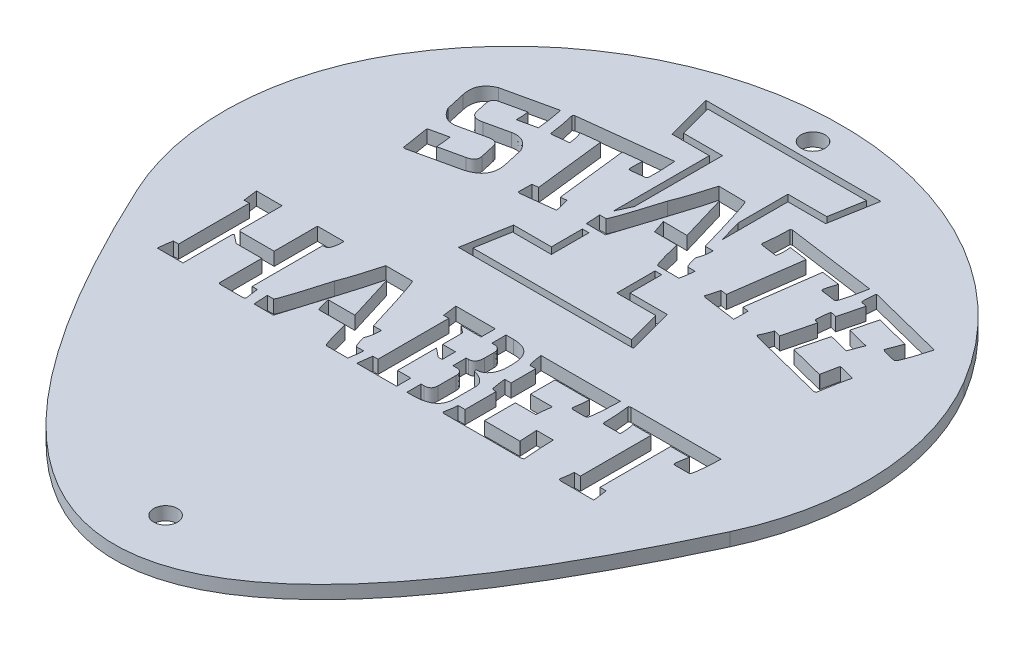
SolidWorks part; units mm, degrees
ref_plane "Front Plane" through (0, 0, 0) normal (0, 0, 1) x (1, 0, 0)
ref_plane "Top Plane" through (0, 0, 0) normal (0, 1, 0) x (1, 0, 0)
ref_plane "Right Plane" through (0, 0, 0) normal (1, 0, 0) x (0, 0, -1)
sketch "Sketch1" plane through (0, 0, 0) normal (0, 1, 0) x (1, 0, 0)
  arc A1 (105.41, 0) -> (-21.59, 0) centre (41.91, 0) ccw
  spline S0 degree 2 poles (-21.59, 0) (41.91, -152.4) (105.41, 0) knots 0 0 0 1 1 1
  dimension "D1" = 63.5
extrude "Boss-Extrude1" add sketch "Sketch1" along normal blind 2.54 contours S0 A1
fillet "Fillet1" radius 50.8 2 edges at (-21.59, 1.27, 0) (105.41, 1.27, 0)
sketch "Sketch2" plane through (0, 2.54, 0) normal (0, 1, 0) x (1, 0, 0)
  line L0 (-19.7843, 6.5271) -> (103.6043, 6.5271) construction
  line L1 (-3.3717, -3.6766) -> (1.5633, -3.6766)
  line L2 (1.5633, -3.6766) -> (1.5633, -11.6703)
  line L3 (1.8983, -12.0053) -> (8.3626, -12.0053)
  line L4 (8.3626, -12.0053) -> (8.3626, -3.6766)
  line L5 (8.3626, -3.6766) -> (13.471, -3.6766)
  line L6 (12.4462, -6.4043) -> (12.1151, -6.4043)
  line L7 (12.1151, -6.4043) -> (12.1151, -19.999)
  line L8 (12.1151, -19.999) -> (13.1241, -19.999)
  line L9 (13.471, -22.5532) -> (13.1241, -22.7266)
  line L10 (13.1241, -22.7266) -> (8.7095, -22.7266)
  line L11 (8.3626, -22.3798) -> (8.3626, -14.3861)
  line L12 (8.3626, -14.3861) -> (3.4277, -14.3861)
  line L13 (3.4277, -14.3861) -> (1.7367, -13.0302)
  line L14 (1.7367, -13.0302) -> (1.5633, -13.3731)
  line L15 (1.5633, -13.3731) -> (1.5633, -22.7266)
  line L16 (1.5633, -22.7266) -> (-3.3717, -22.7266)
  line L17 (-3.0248, -19.999) -> (-2.0158, -19.999)
  line L18 (-2.0158, -19.999) -> (-2.0158, -6.4043)
  line L19 (-2.0158, -6.4043) -> (-3.0248, -6.4043)
  line L20 (21.508, -3.6885) -> (26.6046, -3.6885)
  line L21 (30.3413, -14.9025) -> (31.8706, -14.9025)
  line L22 (31.8706, -14.9025) -> (31.8706, -15.0759)
  line L23 (32.2175, -20.0108) -> (33.5734, -20.0108)
  line L24 (33.2305, -22.7266) -> (29.1588, -22.7266)
  line L25 (27.456, -17.4566) -> (22.3594, -17.4566)
  line L26 (21.6696, -14.9025) -> (26.778, -14.9025)
  line L27 (26.778, -14.9025) -> (24.0504, -6.0692)
  line L28 (24.0504, -6.0692) -> (23.8888, -6.0692)
  line L29 (18.9538, -22.7266) -> (15.2171, -22.7266)
  line L30 (15.2171, -22.7266) -> (15.2171, -22.5532)
  line L31 (15.0437, -20.0108) -> (16.2262, -20.0108)
  line L32 (34.9727, -3.6766) -> (42.5426, -3.6766)
  line L33 (50.1126, -7.9336) -> (50.1126, -9.463)
  line L34 (47.5584, -12.3483) -> (47.5584, -12.6951)
  line L35 (50.286, -15.2375) -> (50.286, -19.321)
  line L36 (45.694, -22.7266) -> (44.6065, -22.7266)
  line L37 (35.3196, -19.999) -> (36.3286, -19.999)
  line L38 (36.3286, -19.999) -> (36.3286, -6.4043)
  line L39 (36.3286, -6.4043) -> (35.3196, -6.4043)
  line L40 (40.0811, -7.5868) -> (40.0811, -11.3274)
  line L41 (40.0811, -11.3274) -> (42.5426, -11.3274)
  line L42 (46.3719, -9.6246) -> (46.3719, -7.7602)
  line L43 (45.5206, -6.4043) -> (44.6065, -6.4043)
  line L44 (40.0811, -12.5217) -> (40.0811, -19.999)
  line L45 (40.0811, -19.999) -> (42.6294, -19.999)
  line L46 (46.5336, -18.6431) -> (46.5336, -15.2375)
  line L47 (45.1776, -13.8816) -> (44.6065, -13.8816)
  line L48 (41.772, -13.8816) -> (40.0811, -12.5217)
  line L49 (51.37, -3.716) -> (66.6439, -3.716)
  line L50 (65.962, -9.664) -> (63.4235, -9.664)
  line L51 (63.4235, -9.664) -> (63.0767, -9.4906)
  line L52 (63.4235, -6.4318) -> (56.7976, -6.4318)
  line L53 (56.7976, -6.4318) -> (56.7976, -11.1776)
  line L54 (56.7976, -11.1776) -> (61.0428, -11.1776)
  line L55 (60.7077, -14.0668) -> (56.7976, -14.0668)
  line L56 (56.7976, -14.0668) -> (56.7976, -20.0108)
  line L57 (56.7976, -20.0108) -> (63.597, -20.0108)
  line L58 (63.597, -20.0108) -> (63.597, -19.8413)
  line L59 (63.4235, -16.621) -> (66.6439, -16.621)
  line L60 (66.9868, -22.5532) -> (66.6439, -22.7266)
  line L61 (66.6439, -22.7266) -> (51.7168, -22.7266)
  line L62 (51.7168, -22.7266) -> (51.37, -22.5532)
  line L63 (51.7168, -20.0108) -> (53.0728, -20.0108)
  line L64 (53.0728, -20.0108) -> (53.0728, -14.0668)
  line L65 (51.8745, -11.1776) -> (53.0728, -11.1776)
  line L66 (53.0728, -11.1776) -> (53.0728, -6.4318)
  line L67 (53.0728, -6.4318) -> (52.0479, -6.4318)
  line L68 (68.6186, -3.6766) -> (85.9658, -3.6766)
  line L69 (85.2879, -9.1161) -> (82.5602, -9.1161)
  line L70 (82.5602, -6.4043) -> (78.9931, -6.4043)
  line L71 (78.9931, -6.4043) -> (78.9931, -19.999)
  line L72 (78.9931, -19.999) -> (80.1795, -19.999)
  line L73 (80.5224, -22.7266) -> (74.0581, -22.7266)
  line L74 (74.0581, -22.7266) -> (73.7112, -22.5532)
  line L75 (74.0581, -19.999) -> (75.2445, -19.999)
  line L76 (75.2445, -19.999) -> (75.2445, -6.4043)
  line L77 (75.2445, -6.4043) -> (71.6773, -6.4043)
  line L78 (72.0084, -9.1161) -> (68.9497, -9.1161)
  line L79 (68.2718, -3.8501) -> (68.6186, -3.6766)
  line L80 (42.5426, -6.4043) -> (38.7094, -6.4043)
  line L82 (42.6294, -19.999) -> (42.6294, -22.7266)
  line L84 (44.6065, -19.999) -> (44.6065, -22.7266)
  line L86 (44.6065, -13.8816) -> (44.6065, -11.3274)
  line L88 (42.5426, -13.8816) -> (42.5426, -11.3274)
  line L90 (44.6065, -6.4043) -> (44.6065, -3.6766)
  line L92 (42.5426, -6.4043) -> (42.5426, -3.6766)
  line L93 (44.6065, -11.3274) -> (45.0042, -11.3274)
  line L94 (42.5426, -13.8816) -> (41.772, -13.8816)
  line L95 (44.6065, -19.999) -> (45.1776, -19.999)
  line L96 (42.6294, -22.7266) -> (34.9727, -22.7266)
  line L97 (44.6065, -3.6766) -> (46.029, -3.6766)
  arc A0 (-12.5617, 32.6356) -> (-15.0576, -14.8714) centre (31.0157, 6.5271) ccw construction
  arc A1 (98.8776, -14.8714) -> (96.3817, 32.6356) centre (52.8043, 6.5271) ccw construction
  spline S0 degree 3 poles (1.5633, -11.6703) (1.5832, -11.7551) (1.6314, -11.9464) (1.818, -12.0103) (1.8983, -12.0053) knots 0 0 0 0 0.531818 1 1 1 1
  spline S1 degree 3 poles (13.471, -3.6766) (13.4667, -4.0745) (13.4563, -4.6352) (13.3372, -5.3157) (13.2327, -5.7059) (13.0884, -6.0101) (12.8646, -6.3061) (12.6103, -6.4071) (12.4462, -6.4043) knots 0 0 0 0 0.377825 0.528227 0.653888 0.759096 0.845794 1 1 1 1
  spline S2 degree 3 poles (13.1241, -19.999) (13.1205, -20.1062) (13.1483, -20.2919) (13.17, -20.5766) (13.215, -20.8686) (13.2577, -21.2152) (13.3552, -21.7812) (13.4101, -22.2356) (13.471, -22.5532) knots 0 0 0 0 0.124228 0.21791 0.332039 0.467782 0.624075 1 1 1 1
  spline S3 degree 3 poles (8.7095, -22.7266) (8.6245, -22.7242) (8.4039, -22.6854) (8.3651, -22.4648) (8.3626, -22.3798) knots 0 0 0 0 0.5 1 1 1 1
  spline S4 degree 3 poles (-3.3717, -22.7266) (-3.377, -22.5722) (-3.3506, -22.3245) (-3.3265, -21.9678) (-3.2826, -21.6466) (-3.2388, -21.2857) (-3.1444, -20.7336) (-3.0861, -20.298) (-3.0248, -19.999) knots 0 0 0 0 0.167857 0.271329 0.389634 0.521087 0.667537 1 1 1 1
  spline S5 degree 3 poles (-3.0248, -6.4043) (-3.085, -6.0443) (-3.1395, -5.5336) (-3.2374, -4.9018) (-3.2802, -4.5265) (-3.3252, -4.2199) (-3.3459, -3.9431) (-3.3736, -3.7707) (-3.3717, -3.6766) knots 0 0 0 0 0.397879 0.560026 0.697261 0.809965 0.897811 1 1 1 1
  spline S6 degree 3 poles (26.6046, -3.6885) (26.6726, -3.7251) (26.7428, -3.8697) (26.8553, -4.108) (26.9794, -4.4176) (27.1277, -4.8125) (27.3075, -5.293) (27.5004, -5.8639) (27.7237, -6.52) (27.9652, -7.265) (28.2404, -8.0962) (28.5287, -9.0174) (28.8448, -10.0253) (29.1891, -11.1185) (29.6866, -12.7557) (30.0827, -14.0236) (30.3413, -14.9025) knots 0 0 0 0 0.018773 0.039327 0.067393 0.103006 0.146294 0.197354 0.255675 0.321893 0.395795 0.477496 0.566465 0.663438 0.767898 1 1 1 1
  spline S7 degree 3 poles (31.8706, -15.0759) (31.8713, -15.5487) (31.7922, -16.476) (31.5364, -17.3711) (31.3661, -17.7917) knots 0 0 0 0 0.510454 1 1 1 1
  spline S8 degree 3 poles (31.3661, -17.7917) (31.4421, -18.1183) (31.5716, -18.5683) (31.7384, -19.1226) (31.849, -19.4351) (31.948, -19.6816) (32.0548, -19.8793) (32.1392, -19.998) (32.2175, -20.0108) knots 0 0 0 0 0.415941 0.581563 0.718283 0.827951 0.909707 1 1 1 1
  spline S9 degree 3 poles (33.5734, -20.0108) (33.5746, -20.1622) (33.5607, -20.4083) (33.526, -20.7615) (33.4853, -21.0831) (33.4392, -21.4422) (33.3552, -21.9943) (33.2807, -22.4258) (33.2305, -22.7266) knots 0 0 0 0 0.165637 0.269704 0.388543 0.520588 0.666057 1 1 1 1
  spline S10 degree 3 poles (29.1588, -22.7266) (29.1039, -22.7222) (29.0345, -22.6537) (28.9525, -22.5312) (28.8759, -22.3844) (28.7891, -22.1997) (28.6986, -21.9732) (28.6062, -21.7051) (28.5027, -21.3967) (28.3938, -21.0467) (28.274, -20.6559) (28.1532, -20.2232) (28.0272, -19.7485) (27.894, -19.2332) (27.6965, -18.466) (27.5556, -17.8679) (27.456, -17.4566) knots 0 0 0 0 0.0276 0.04989 0.079536 0.116114 0.159439 0.210268 0.268221 0.333986 0.406901 0.487456 0.574996 0.670392 0.772966 1 1 1 1
  spline S11 degree 3 poles (22.3594, -17.4566) (22.2573, -17.1495) (22.1095, -16.7143) (21.9408, -16.1612) (21.8463, -15.8178) (21.7712, -15.5222) (21.7021, -15.2243) (21.6739, -15.0217) (21.6696, -14.9025) knots 0 0 0 0 0.366212 0.519992 0.654155 0.76917 0.86511 1 1 1 1
  spline S12 degree 3 poles (23.8888, -6.0692) (23.8894, -6.1187) (23.87, -6.2062) (23.845, -6.3433) (23.8067, -6.4895) (23.7646, -6.6659) (23.7135, -6.8725) (23.6488, -7.1083) (23.5801, -7.376) (23.4947, -7.6718) (23.4066, -7.9987) (23.3015, -8.3537) (23.1929, -8.7408) (23.07, -9.1568) (22.9392, -9.6033) (22.8032, -10.0799) (22.651, -10.5846) (22.4958, -11.1205) (22.3238, -11.6843) (22.1482, -12.2804) (21.958, -12.9052) (21.7617, -13.5614) (21.5523, -14.2454) (21.3349, -14.96) (21.1118, -15.7045) (20.874, -16.4793) (20.6254, -17.2825) (20.3756, -18.1188) (20.1035, -18.9796) (19.8343, -19.876) (19.4506, -21.1285) (19.1497, -22.0803) (18.9538, -22.7266) knots 0 0 0 0 0.008482 0.015422 0.024059 0.034567 0.046726 0.060811 0.076767 0.094434 0.113971 0.13522 0.158339 0.183391 0.210094 0.238665 0.268953 0.301108 0.33498 0.370721 0.408395 0.44772 0.488979 0.531889 0.576668 0.623164 0.671811 0.721826 0.773842 0.827659 0.88341 1 1 1 1
  spline S13 degree 3 poles (15.2171, -22.5532) (15.1916, -22.2327) (15.1585, -21.7792) (15.1106, -21.2106) (15.0892, -20.8661) (15.067, -20.576) (15.0544, -20.2973) (15.0462, -20.1147) (15.0437, -20.0108) knots 0 0 0 0 0.378522 0.535222 0.671642 0.784811 0.877726 1 1 1 1
  spline S14 degree 3 poles (16.2262, -20.0108) (16.2917, -19.9701) (16.3643, -19.8411) (16.4695, -19.6301) (16.581, -19.3753) (16.6983, -19.0519) (16.8428, -18.6656) (16.9991, -18.2118) (17.1717, -17.6925) (17.3621, -17.1069) (17.5655, -16.4547) (17.7857, -15.7354) (18.0281, -14.9524) (18.2788, -14.1001) (18.6479, -12.8309) (18.9384, -11.847) (19.1273, -11.1658) knots 0 0 0 0 0.02398 0.046649 0.076156 0.113186 0.157286 0.208717 0.26749 0.333211 0.40669 0.487124 0.575043 0.670203 0.772728 1 1 1 1
  spline S15 degree 3 poles (19.1273, -11.1658) (19.3002, -10.7717) (19.547, -10.1164) (19.8746, -9.1629) (20.1628, -8.2844) (20.4667, -7.2921) (20.9331, -5.7521) (21.2728, -4.536) (21.508, -3.6885) knots 0 0 0 0 0.16438 0.267414 0.385207 0.517635 0.663905 1 1 1 1
  spline S16 degree 3 poles (46.029, -3.6766) (46.3493, -3.6748) (46.8161, -3.7054) (47.4103, -3.8186) (47.8112, -3.9316) (48.1806, -4.0816) (48.5172, -4.268) (48.8231, -4.4858) (49.0982, -4.7362) (49.3398, -5.0208) (49.5442, -5.3411) (49.7252, -5.6888) (49.8638, -6.0758) (49.9799, -6.4928) (50.0849, -7.1147) (50.1132, -7.6003) (50.1126, -7.9336) knots 0 0 0 0 0.141988 0.206643 0.267847 0.326362 0.382935 0.43805 0.49247 0.547434 0.603008 0.660577 0.72084 0.784848 0.852262 1 1 1 1
  spline S17 degree 3 poles (50.1126, -9.463) (50.0363, -9.8918) (49.8884, -10.502) (49.539, -11.2131) (49.2421, -11.6284) (48.8935, -11.9533) (48.3485, -12.2663) (47.8762, -12.3541) (47.5584, -12.3483) knots 0 0 0 0 0.309204 0.44026 0.558794 0.668748 0.775024 1 1 1 1
  spline S18 degree 3 poles (47.5584, -12.6951) (47.967, -12.8154) (48.5443, -13.0199) (49.213, -13.4078) (49.6022, -13.7131) (49.9107, -14.0465) (50.202, -14.5387) (50.2864, -14.9594) (50.286, -15.2375) knots 0 0 0 0 0.318967 0.454552 0.576178 0.687424 0.792188 1 1 1 1
  spline S19 degree 3 poles (50.286, -19.321) (50.2819, -19.5873) (50.2563, -19.9802) (50.1334, -20.476) (50.0052, -20.8115) (49.8455, -21.1207) (49.6426, -21.3997) (49.4123, -21.6578) (49.1381, -21.884) (48.8321, -22.0852) (48.4859, -22.2538) (48.1104, -22.405) (47.6947, -22.5206) (47.2463, -22.6174) (46.5751, -22.6969) (46.0539, -22.7342) (45.694, -22.7266) knots 0 0 0 0 0.122782 0.180144 0.234516 0.287818 0.339851 0.39295 0.446621 0.502992 0.561152 0.623604 0.689077 0.759544 0.834572 1 1 1 1
  spline S20 degree 3 poles (34.9727, -22.7266) (34.9708, -22.6326) (34.9985, -22.4602) (35.0192, -22.1833) (35.0642, -21.8768) (35.107, -21.5014) (35.2049, -20.8696) (35.2594, -20.3589) (35.3196, -19.999) knots 0 0 0 0 0.102189 0.190035 0.302739 0.439974 0.602121 1 1 1 1
  spline S21 degree 3 poles (35.3196, -6.4043) (35.2594, -6.0443) (35.2049, -5.5336) (35.107, -4.9018) (35.0642, -4.5265) (35.0192, -4.2199) (34.9985, -3.9431) (34.9708, -3.7707) (34.9727, -3.6766) knots 0 0 0 0 0.397879 0.560026 0.697261 0.809965 0.897811 1 1 1 1
  spline S22 degree 3 poles (38.7094, -6.4043) (38.9097, -6.5584) (39.1926, -6.7724) (39.5313, -7.0511) (39.7261, -7.2119) (39.8759, -7.3454) (39.9959, -7.4612) (40.0685, -7.535) (40.0811, -7.5868) knots 0 0 0 0 0.416958 0.584812 0.72325 0.833736 0.914955 1 1 1 1
  spline S23 degree 3 poles (45.0042, -11.3274) (45.2053, -11.3232) (45.5077, -11.2897) (45.842, -11.0955) (46.0419, -10.9053) (46.1922, -10.6572) (46.3412, -10.2319) (46.3759, -9.8748) (46.3719, -9.6246) knots 0 0 0 0 0.245182 0.352852 0.460208 0.573842 0.698393 1 1 1 1
  spline S24 degree 3 poles (46.3719, -7.7602) (46.3734, -7.6144) (46.3508, -7.3992) (46.2593, -7.1322) (46.163, -6.954) (46.0438, -6.7894) (45.8405, -6.5881) (45.6543, -6.4704) (45.5206, -6.4043) knots 0 0 0 0 0.257766 0.378193 0.496611 0.614573 0.73607 1 1 1 1
  spline S25 degree 3 poles (45.1776, -19.999) (45.3799, -20.0061) (45.6655, -19.9627) (46.0079, -19.8225) (46.2007, -19.666) (46.3573, -19.4716) (46.5033, -19.1313) (46.5364, -18.8426) (46.5336, -18.6431) knots 0 0 0 0 0.274588 0.390158 0.499896 0.609633 0.72757 1 1 1 1
  spline S26 degree 3 poles (46.5336, -15.2375) (46.5343, -15.0374) (46.506, -14.7468) (46.356, -14.4083) (46.201, -14.2142) (46.0068, -14.0591) (45.6683, -13.9091) (45.3777, -13.8809) (45.1776, -13.8816) knots 0 0 0 0 0.274057 0.390311 0.5 0.609689 0.725943 1 1 1 1
  spline S27 degree 3 poles (66.6439, -3.716) (66.6277, -4.1811) (66.6089, -4.8554) (66.5706, -5.7225) (66.5398, -6.3033) (66.503, -6.8379) (66.4696, -7.327) (66.4287, -7.7682) (66.3912, -8.1628) (66.3476, -8.511) (66.3021, -8.8137) (66.25, -9.0698) (66.2017, -9.28) (66.1469, -9.4427) (66.0846, -9.5807) (66.0206, -9.66) (65.962, -9.664) knots 0 0 0 0 0.230352 0.333856 0.429597 0.518237 0.599091 0.672218 0.737577 0.795252 0.845932 0.889041 0.924531 0.952707 0.973649 1 1 1 1
  spline S28 degree 3 poles (63.0767, -9.4906) (63.131, -9.1323) (63.2035, -8.6214) (63.2891, -7.9735) (63.3343, -7.5657) (63.3761, -7.2087) (63.4094, -6.8371) (63.4245, -6.5832) (63.4235, -6.4318) knots 0 0 0 0 0.352909 0.50259 0.636562 0.752444 0.852662 1 1 1 1
  spline S29 degree 3 poles (61.0428, -11.1776) (60.9895, -11.5251) (60.9247, -12.0209) (60.8394, -12.6449) (60.7911, -13.0324) (60.7571, -13.3665) (60.7216, -13.7049) (60.7073, -13.9325) (60.7077, -14.0668) knots 0 0 0 0 0.362431 0.515491 0.649224 0.765001 0.861638 1 1 1 1
  spline S30 degree 3 poles (63.597, -19.8413) (63.5716, -19.4367) (63.5381, -18.8637) (63.4906, -18.1453) (63.4687, -17.7076) (63.447, -17.3385) (63.4342, -16.9837) (63.4259, -16.7525) (63.4235, -16.621) knots 0 0 0 0 0.377135 0.533875 0.669731 0.784774 0.877729 1 1 1 1
  spline S31 degree 3 poles (66.6439, -16.621) (66.6424, -17.0284) (66.6545, -17.6619) (66.69, -18.5356) (66.7309, -19.2555) (66.7773, -20.019) (66.8584, -21.1231) (66.9359, -21.9726) (66.9868, -22.5532) knots 0 0 0 0 0.205603 0.319754 0.441286 0.569516 0.705819 1 1 1 1
  spline S32 degree 3 poles (51.37, -22.5532) (51.4772, -22.0748) (51.6274, -21.2311) (51.7198, -20.3783) (51.7168, -20.0108) knots 0 0 0 0 0.572014 1 1 1 1
  spline S33 degree 3 poles (53.0728, -14.0668) (52.9491, -14.068) (52.774, -14.0621) (52.5612, -14.0241) (52.4391, -13.9887) (52.3416, -13.945) (52.2569, -13.8624) (52.214, -13.7888) (52.2214, -13.7318) knots 0 0 0 0 0.371737 0.524226 0.647832 0.753726 0.840279 1 1 1 1
  spline S34 degree 3 poles (52.2214, -13.7318) (52.1595, -13.4408) (52.1036, -13.0192) (52.0075, -12.4885) (51.9642, -12.1485) (51.9197, -11.8498) (51.8966, -11.5297) (51.8693, -11.3111) (51.8745, -11.1776) knots 0 0 0 0 0.345623 0.494312 0.626973 0.744084 0.845332 1 1 1 1
  spline S35 degree 3 poles (52.0479, -6.4318) (51.9602, -6.4129) (51.8788, -6.2663) (51.7821, -6.0279) (51.7047, -5.7262) (51.6161, -5.3451) (51.5036, -4.6646) (51.418, -4.1131) (51.37, -3.716) knots 0 0 0 0 0.085765 0.166449 0.274219 0.411848 0.579054 1 1 1 1
  spline S36 degree 3 poles (85.9658, -3.6766) (85.9446, -4.101) (85.9187, -4.7176) (85.8686, -5.5109) (85.833, -6.043) (85.7991, -6.532) (85.7588, -6.9773) (85.7192, -7.3806) (85.6814, -7.7423) (85.6388, -8.0619) (85.5912, -8.3377) (85.5442, -8.5718) (85.4986, -8.7626) (85.453, -8.9138) (85.3936, -9.0366) (85.3423, -9.1147) (85.2879, -9.1161) knots 0 0 0 0 0.229959 0.333973 0.430181 0.518586 0.599251 0.672128 0.737933 0.796058 0.84656 0.889372 0.925244 0.952903 0.974211 1 1 1 1
  spline S37 degree 3 poles (82.5602, -9.1161) (82.4734, -9.119) (82.2622, -9.0772) (82.2121, -8.8693) (82.2134, -8.785) knots 0 0 0 0 0.509252 1 1 1 1
  spline S38 degree 3 poles (82.2134, -8.785) (82.2084, -8.6568) (82.235, -8.4486) (82.259, -8.1443) (82.3021, -7.8652) (82.3469, -7.549) (82.4415, -7.0602) (82.4994, -6.6716) (82.5602, -6.4043) knots 0 0 0 0 0.159143 0.261079 0.380037 0.510802 0.658785 1 1 1 1
  spline S39 degree 3 poles (80.1795, -19.999) (80.2274, -20.3606) (80.3006, -20.8686) (80.3864, -21.5018) (80.4322, -21.8767) (80.4732, -22.1838) (80.5048, -22.4595) (80.5218, -22.633) (80.5224, -22.7266) knots 0 0 0 0 0.397951 0.559933 0.697195 0.809921 0.897937 1 1 1 1
  spline S40 degree 3 poles (73.7112, -22.5532) (73.7651, -22.2343) (73.837, -21.7825) (73.9229, -21.2147) (73.9683, -20.8687) (74.0098, -20.5762) (74.0423, -20.2926) (74.0586, -20.1058) (74.0581, -19.999) knots 0 0 0 0 0.37615 0.532208 0.66795 0.782077 0.87592 1 1 1 1
  spline S41 degree 3 poles (71.6773, -6.4043) (71.8067, -6.7754) (71.9736, -7.678) (72.0095, -8.5936) (72.0084, -9.1161) knots 0 0 0 0 0.428461 1 1 1 1
  spline S42 degree 3 poles (68.9497, -9.1161) (68.8636, -9.1227) (68.665, -9.0698) (68.6121, -8.8711) (68.6186, -8.785) knots 0 0 0 0 0.5 1 1 1 1
  spline S43 degree 3 poles (68.6186, -8.785) (68.6237, -7.9826) (68.5507, -6.3332) (68.3895, -4.6902) (68.2718, -3.8501) knots 0 0 0 0 0.486078 1 1 1 1
  dimension "D1" = 2.0638
  dimension "D2" = 1.9771
extrude "Cut-Extrude2" cut sketch "Sketch2" against normal blind 2.54
sketch "Sketch3" plane through (0, 2.54, 0) normal (0, 1, 0) x (1, 0, 0)
  arc A0 (-12.5617, 32.6356) -> (-15.0576, -14.8714) centre (31.0157, 6.5271) ccw construction
  arc A1 (98.8776, -14.8714) -> (96.3817, 32.6356) centre (52.8043, 6.5271) ccw construction
  spline S0 degree 2 poles (-19.7144, 9.1923) (41.91, 36.5277) (103.5344, 9.1923) knots 0 0 0 1 1 1 construction
  text T0 " STATE" font "NCAA Iowa St Cyclone" height 19.05
  point P5 (41.91, 0)
  point P15 (-19.7144, 9.1923)
  point P18 (103.5344, 9.1923)
  dimension "D1" = 22.86
extrude "Cut-Extrude3" cut sketch "Sketch3" against normal blind 2.54
sketch "Sketch4" plane through (0, 2.54, 0) normal (0, 1, 0) x (1, 0, 0)
  line L0 (26.95, 7.62) -> (57.43, 7.62)
  line L23 (35.56, 14.0941) -> (48.26, 46.8659) construction
  line L24 (34.29, 15.3641) -> (27.0259, 15.3641)
  line L25 (27.0259, 15.3641) -> (25.4364, 6.35)
  line L27 (57.43, 7.62) -> (55.7285, 13.97)
  line L29 (55.7285, 13.97) -> (48.26, 13.97)
  line L31 (48.26, 13.97) -> (48.26, 21.316)
  line L33 (48.26, 46.8659) -> (55.7285, 46.8659)
  line L34 (55.7285, 46.8659) -> (56.87, 53.34)
  line L35 (56.87, 53.34) -> (26.39, 53.34)
  line L37 (35.56, 46.99) -> (35.56, 30.0693)
  line L38 (35.56, 14.0941) -> (28.0915, 14.0941)
  line L39 (28.0915, 14.0941) -> (26.95, 7.62)
  line L40 (35.56, 46.99) -> (28.0915, 46.99)
  line L41 (28.0915, 46.99) -> (26.39, 53.34)
  line L42 (25.4364, 6.35) -> (59.0851, 6.35)
  line L43 (59.0851, 6.35) -> (56.703, 15.24)
  line L44 (56.703, 15.24) -> (49.53, 15.24)
  line L45 (49.53, 15.24) -> (49.53, 21.316)
  line L46 (49.53, 45.5959) -> (56.7941, 45.5959)
  line L47 (56.7941, 45.5959) -> (58.3836, 54.61)
  line L48 (58.3836, 54.61) -> (24.7349, 54.61)
  line L49 (27.117, 45.72) -> (24.7349, 54.61)
  line L50 (34.29, 45.72) -> (27.117, 45.72)
  line L51 (34.29, 45.72) -> (34.29, 27.2574)
  line L52 (35.56, 15.3641) -> (27.0259, 15.3641) construction
  line L53 (48.26, 21.316) -> (49.53, 21.316)
  line L54 (34.29, 21.316) -> (35.56, 21.316)
  line L55 (35.56, 30.0693) -> (34.29, 27.2574)
  line L57 (48.26, 32.7297) -> (48.9825, 30.2498) construction
  line L58 (49.53, 32.9109) -> (49.53, 45.5959)
  line L59 (49.53, 32.9109) -> (48.26, 37.2701)
  line L60 (35.56, 21.316) -> (35.56, 14.0941)
  line L61 (35.56, 46.99) -> (35.56, 14.0941) construction
  line L62 (34.29, 21.316) -> (34.29, 15.3641)
  line L63 (34.29, 45.72) -> (34.29, 14.0941) construction
  line L64 (49.53, 15.24) -> (49.53, 46.8659) construction
  line L65 (48.26, 37.2701) -> (48.26, 46.8659)
  line L66 (48.26, 13.97) -> (48.26, 46.8659) construction
  line L67 (48.26, 45.5959) -> (56.7941, 45.5959) construction
  line L68 (35.56, 30.0693) -> (35.56, 21.316) construction
  line L69 (34.29, 27.2574) -> (34.29, 21.316) construction
  line L70 (49.53, 32.9109) -> (49.53, 21.316) construction
  line L71 (48.26, 37.2701) -> (48.26, 21.316) construction
  line L72 (34.8044, 25.3109) -> (35.56, 26.9839) construction
  line L73 (35.56, 30.0693) -> (35.56, 21.316) construction
  line L75 (37.5005, 22.5636) -> (33.7638, 22.6069) construction
  spline S0 degree 3 poles (45.3838, 41.5072) (45.4032, 41.4936) (45.4656, 41.4501) (45.5294, 41.301) (45.6307, 41.084) (45.7499, 40.7736) (45.8963, 40.3788) (46.065, 39.8952) (46.2526, 39.3227) (46.4665, 38.6635) (46.7015, 37.9154) (46.963, 37.0806) (47.2407, 36.1554) (47.5498, 35.145) (47.8766, 34.0452) (48.2211, 32.8573) (48.5989, 31.5846) (48.8518, 30.7046) (48.9825, 30.2498) knots 0 0 0 0 0.005928 0.019061 0.039478 0.067423 0.102922 0.146303 0.197155 0.255589 0.321925 0.395848 0.477262 0.566679 0.663591 0.767999 0.880091 1 1 1 1 construction
  spline S2 degree 3 poles (34.8044, 25.3109) (34.8264, 25.3284) (34.8857, 25.3756) (34.9583, 25.5038) (35.0522, 25.6892) (35.1669, 25.9411) (35.2888, 26.2636) (35.4415, 26.646) (35.6006, 27.1) (35.7834, 27.6162) (35.973, 28.2035) (36.1931, 28.8501) (36.4197, 29.5677) (36.6682, 30.349) (36.9324, 31.1978) (37.2124, 32.1122) (37.507, 33.0944) (37.7106, 33.771) (37.8158, 34.1205) knots 0 0 0 0 0.008979 0.024207 0.046495 0.07617 0.112953 0.157345 0.208511 0.267548 0.333392 0.406847 0.48712 0.575277 0.670388 0.772856 0.882686 1 1 1 1 construction
  point P2 (41.91, 0)
  point P3 (41.91, 30.48)
  dimension "D1" = 75
  dimension "D2" = 80
  dimension "D3" = 6.35
  dimension "D4" = 12.7
  dimension "D5" = 45.72
  dimension "D6" = 30.48
  dimension "D7" = 30.48
  dimension "D8" = 1.27
  dimension "D10" = 1.27
  dimension "D11" = 1.27
  dimension "D12" = 16.9207
  dimension "D13" = 7.4685
  dimension "D14" = 18.4626
  dimension "D9" = 1.27
extrude "Cut-Extrude4" cut sketch "Sketch4" against normal blind 2.54
sketch "Sketch5" plane through (0, 2.54, 0) normal (0, 1, 0) x (1, 0, 0)
  line L0 (-19.7843, 6.5271) -> (103.6043, 6.5271) construction
  line L1 (41.91, 60.325) -> (41.91, 63.5) construction
  circle A0 centre (41.91, 58.039) radius 2.286
  circle A1 centre (41.91, -66.421) radius 2.286
  arc A2 (-12.5617, 32.6356) -> (-15.0576, -14.8714) centre (31.0157, 6.5271) ccw construction
  arc A3 (98.8776, -14.8714) -> (96.3817, 32.6356) centre (52.8043, 6.5271) ccw construction
  arc A4 (96.3817, 32.6356) -> (-12.5617, 32.6356) centre (41.91, 0) ccw construction
  point P4 (41.91, 6.5271)
  dimension "D1" = 4.572
  dimension "D3" = 124.46
  dimension "D2" = 3.175
extrude "Cut-Extrude5" cut sketch "Sketch5" against normal blind 2.54
sketch "Sketch6" plane through (0, 2.54, 0) normal (0, 1, 0) x (1, 0, 0)
  line L0 (40.3109, 30.3562) -> (40.8297, 30.3498)
  line L1 (40.3109, 30.3562) -> (45.4192, 30.2932) construction
  line L2 (40.8297, 30.3498) -> (41.719, 27.7815)
  line L3 (46.0657, 27.7311) -> (40.9691, 27.7902) construction
  line L4 (41.719, 27.7815) -> (40.9691, 27.7902)
  spline S0 degree 3 poles (-2781.9615, -984.9793) (75.2417, -25.0649) (49.8362, -0.8924) (40.6844, 28.701) (40.5719, 29.0931) (40.4739, 29.4375) (40.4042, 29.7353) (40.3526, 29.9848) (39.4237, 35.0657) (70.9958, 43.1739) (-2947.1747, -240.8053) knots -34.480634 -34.480634 -34.480634 -34.480634 0.192989 0.365344 0.519928 0.653918 0.769874 0.865378 0.942022 6.590865 6.590865 6.590865 6.590865 only from (40.9691, 27.7902) to (40.3109, 30.3562) construction
  spline S1 degree 3 poles (40.9691, 27.7902) (40.9177, 27.9531) (40.8204, 28.2614) (40.6844, 28.701) (40.5719, 29.0931) (40.4739, 29.4375) (40.4042, 29.7353) (40.3526, 29.9848) (40.3159, 30.1857) (40.3124, 30.3049) (40.3109, 30.3562) knots 0 0 0 0 0.192989 0.365344 0.519928 0.653918 0.769874 0.865378 0.942022 1 1 1 1
extrude "Boss-Extrude2" add sketch "Sketch6" against normal up to surface (2.54 mm away) up to face at (41.91, 0, -55.753)
